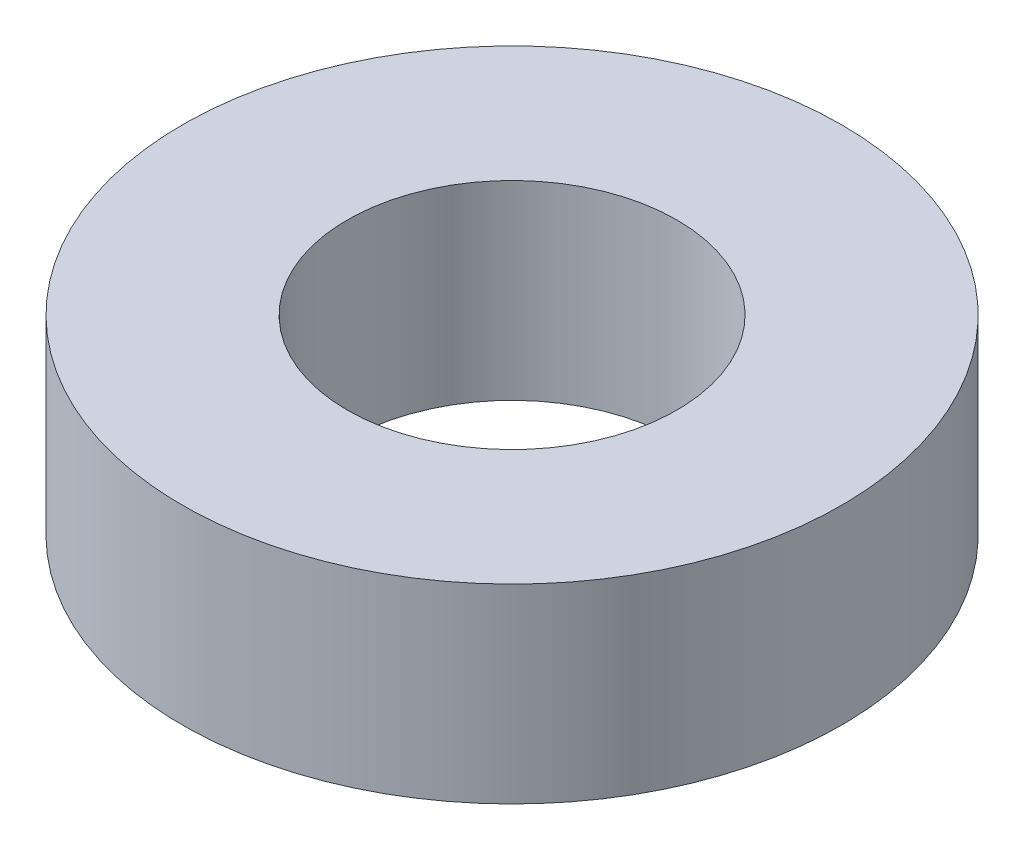
SolidWorks part; units mm, degrees
ref_plane "Front Plane" through (0, 0, 0) normal (0, 0, 1) x (1, 0, 0)
ref_plane "Top Plane" through (0, 0, 0) normal (0, 1, 0) x (1, 0, 0)
ref_plane "Right Plane" through (0, 0, 0) normal (1, 0, 0) x (0, 0, -1)
sketch "Sketch1" plane through (0, 0, 0) normal (0, 1, 0) x (1, 0, 0)
  circle A0 centre (0, 0) radius 45
  dimension "FLANGE_OD" = 90
extrude "Boss-Extrude1" add sketch "Sketch1" along normal blind 26
sketch "Sketch2" plane through (0, 0, 0) normal (0, 1, 0) x (1, 0, 0)
  circle A0 centre (0, 0) radius 22.5
  dimension "BORE_D" = 45
extrude "Cut-Extrude1" cut sketch "Sketch2" along normal through all
sketch "Sketch3" plane through (0, 26, 0) normal (0, 1, 0) x (1, 0, 0)
  circle A0 centre (0, 0) radius 16.6928 construction
  circle A1 centre (-16.6928, 0) radius 1.6511
  dimension "BOLT_D" = 3.3023
  dimension "BOLT_PCD" = 33.3857
extrude "Cut-Extrude2" cut sketch "Sketch3" against normal blind 23.3188 rebuild error yes
pattern_circular "CirPattern1" count 6 over 360 rebuild error yes
